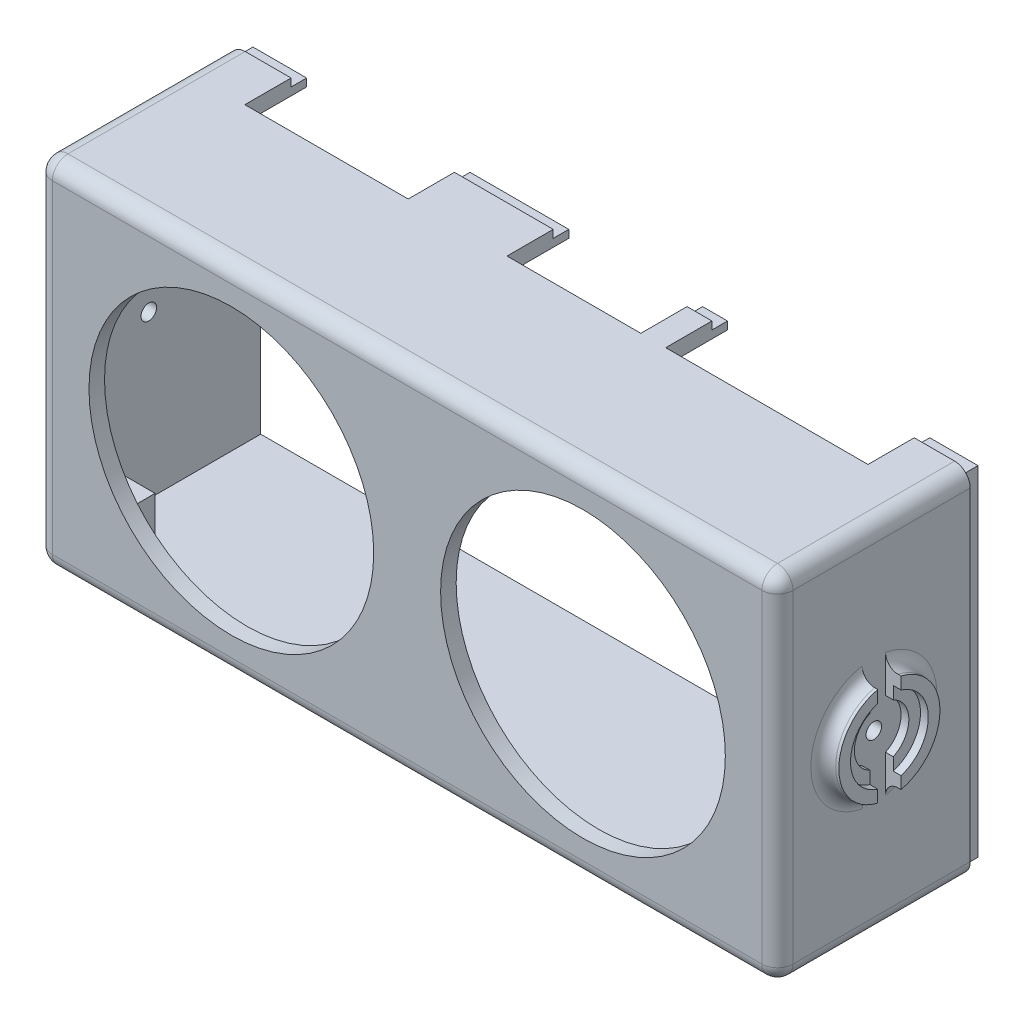
SolidWorks part; units mm, degrees
ref_plane "Спереди" through (0, 0, 0) normal (0, 0, 1) x (1, 0, 0)
ref_plane "Сверху" through (0, 0, 0) normal (0, 1, 0) x (1, 0, 0)
ref_plane "Справа" through (0, 0, 0) normal (1, 0, 0) x (0, 0, -1)
sketch "Эскиз1" plane through (0, 0, 0) normal (0, 0, 1) x (1, 0, 0)
  line L1 (-45.4, -0.2) -> (0.2, -0.2)
  line L2 (-45.4, -0.2) -> (-45.4, 20.6)
  line L3 (-45.4, 20.6) -> (0.2, 20.6)
  line L4 (0.2, -0.2) -> (0.2, 20.6)
  line L5 (1.2, 21.6) -> (-46.4, 21.6)
  line L6 (1.2, 21.6) -> (1.2, -1.2)
  line L7 (1.2, -1.2) -> (-46.4, -1.2)
  line L8 (-46.4, 21.6) -> (-46.4, -1.2)
extrude "Бобышка-Вытянуть1" add sketch "Эскиз1" along normal offset from surface (11.389 mm away) 3 offset beyond the face yes
sketch "Эскиз2" plane through (0, 0, 11.389) normal (0, 0, 1) x (1, 0, 0)
  line L1 (1.2, 21.6) -> (-46.4, 21.6)
  line L2 (1.2, 21.6) -> (1.2, -1.2)
  line L3 (1.2, -1.2) -> (-46.4, -1.2)
  line L4 (-46.4, 21.6) -> (-46.4, -1.2)
extrude "Бобышка-Вытянуть2" add sketch "Эскиз2" along normal blind 1
sketch "Эскиз3" plane through (0, 0, 12.389) normal (0, 0, 1) x (1, 0, 0)
  circle A0 centre (-11.3, 10.2) radius 9.15
  circle A1 centre (-33.9, 10.2) radius 9.15
  dimension "D1" = 18.3
extrude "Вырез-Вытянуть1" cut sketch "Эскиз3" against normal up to surface (1 mm away) up to face at (-22.6, 10.2, 11.389)
sketch "Эскиз7" plane through (0, 21.6, 0) normal (0, 1, 0) x (1, 0, 0)
  line L0 (-42.1499, -2.6711) -> (-32.2499, -2.6711) construction
  line L1 (-25.2999, -2.6711) -> (-17.2999, -2.6711) construction
  line L2 (-15.1001, -2.6711) -> (-2.7001, -2.6711) construction
  line L3 (1.2, 0) -> (-46.4, 0) construction
  line L4 (-2.4001, 0) -> (-15.4001, 0)
  line L5 (-2.4001, 0) -> (-2.4001, -2.9711)
  line L6 (-2.4001, -2.9711) -> (-15.4001, -2.9711)
  line L7 (-15.4001, 0) -> (-15.4001, -2.9711)
  line L9 (-16.9999, 0) -> (-25.5999, 0)
  line L10 (-16.9999, 0) -> (-16.9999, -2.9711)
  line L11 (-16.9999, -2.9711) -> (-25.5999, -2.9711)
  line L12 (-25.5999, 0) -> (-25.5999, -2.9711)
  line L13 (-31.9499, 0) -> (-42.4499, 0)
  line L14 (-31.9499, 0) -> (-31.9499, -2.9711)
  line L15 (-31.9499, -2.9711) -> (-42.4499, -2.9711)
  line L16 (-42.4499, 0) -> (-42.4499, -2.9711)
  dimension "D1" = 0.3
  dimension "D2" = 0.3
  dimension "D3" = 0.3
  dimension "D4" = 0.3
  dimension "D5" = 0.3
  dimension "D6" = 0.3
  dimension "D7" = 0.3
  dimension "D8" = 0.3
  dimension "D9" = 0.3
extrude "Вырез-Вытянуть2" cut sketch "Эскиз7" against normal up to surface (1 mm away) up to face at (-22.6, 20.6, 5.6945)
sketch "Эскиз8" plane through (1.2, 0, 0) normal (1, 0, 0) x (0, 0, -1)
  line L0 (-12.389, 10.2) -> (0, 10.2) construction
  line L1 (-12.389, -1.2) -> (-12.389, 21.6) construction
  line L2 (0, -1.2) -> (0, 21.6) construction
  line L3 (-6.1945, 21.6) -> (-6.1945, -1.2) construction
  line L4 (-12.389, 21.6) -> (0, 21.6) construction
  line L5 (-12.389, -1.2) -> (0, -1.2) construction
  circle A0 centre (-6.1945, 10.2) radius 1.75
  circle A1 centre (-6.1945, 10.2) radius 3.25
  dimension "D1" = 3.5
  dimension "D2" = 1.5
extrude "Бобышка-Вытянуть3" add sketch "Эскиз8" along normal blind 1
sketch "Эскиз9" plane through (2.2, 0, 0) normal (1, 0, 0) x (0, 0, -1)
  line L1 (-6.9445, 6.95) -> (-5.4445, 6.95)
  line L2 (-6.9445, 6.95) -> (-6.9445, 13.45)
  line L3 (-6.9445, 13.45) -> (-5.4445, 13.45)
  line L4 (-5.4445, 6.95) -> (-5.4445, 13.45)
  line L5 (-6.9445, 6.95) -> (-5.4445, 13.45) construction
  line L6 (-6.9445, 13.45) -> (-5.4445, 6.95) construction
  circle A0 centre (-6.1945, 10.2) radius 3.25 construction
  point P0 (-6.1945, 10.2)
  dimension "D1" = 1.5
extrude "Вырез-Вытянуть3" cut sketch "Эскиз9" against normal up to surface (1 mm away) up to face at (1.2, 10.2, 2.9445)
sketch "Эскиз10" plane through (2.2, 0, 0) normal (1, 0, 0) x (0, 0, -1)
  line L0 (-4.4445, 10.2) -> (-2.9445, 10.2) construction
  arc A1 (-5.4445, 8.6189) -> (-5.4445, 11.7811) centre (-6.1945, 10.2) ccw construction
  arc A2 (-5.4445, 7.0377) -> (-5.4445, 13.3623) centre (-6.1945, 10.2) ccw construction
  circle A3 centre (-6.1945, 10.2) radius 2.5
  point P2 (-3.6945, 10.2)
extrude "Вырез-Вытянуть6" cut sketch "Эскиз10" against normal blind 0.5
sketch "Эскиз13" plane through (1.2, 0, 0) normal (1, 0, 0) x (0, 0, -1)
  circle A0 centre (-6.1945, 10.2) radius 0.5
  dimension "D1" = 1
extrude "Вырез-Вытянуть7" cut sketch "Эскиз13" against normal up to surface (1 mm away) up to face at (0.2, 10.2, 5.6945)
sketch "Эскиз15" plane through (-46.4, 0, 0) normal (-1, 0, 0) x (0, 0, 1)
  line L0 (0, 10.2) -> (12.389, 10.2) construction
  line L1 (0, 21.6) -> (0, -1.2) construction
  line L2 (12.389, 21.6) -> (12.389, -1.2) construction
  line L3 (6.1945, 21.6) -> (6.1945, -1.2) construction
  line L4 (12.389, 21.6) -> (0, 21.6) construction
  line L5 (12.389, -1.2) -> (0, -1.2) construction
  circle A0 centre (6.1945, 10.2) radius 1.75
  circle A1 centre (6.1945, 10.2) radius 3.25
  dimension "D1" = 3.5
  dimension "D2" = 1.5
extrude "Бобышка-Вытянуть4" add sketch "Эскиз15" along normal blind 1
sketch "Эскиз16" plane through (-47.4, 0, 0) normal (-1, 0, 0) x (0, 0, 1)
  line L0 (2.9445, 10.2) -> (4.4445, 10.2) construction
  circle A0 centre (6.1945, 10.2) radius 3.25 construction
  circle A1 centre (6.1945, 10.2) radius 1.75 construction
  circle A2 centre (6.1945, 10.2) radius 2.5
  point P9 (3.6945, 10.2)
extrude "Вырез-Вытянуть8" cut sketch "Эскиз16" against normal blind 0.5
sketch "Эскиз17" plane through (-47.4, 0, 0) normal (-1, 0, 0) x (0, 0, 1)
  line L1 (6.9445, 6.95) -> (5.4445, 6.95)
  line L2 (6.9445, 6.95) -> (6.9445, 13.45)
  line L3 (6.9445, 13.45) -> (5.4445, 13.45)
  line L4 (5.4445, 6.95) -> (5.4445, 13.45)
  line L5 (6.9445, 6.95) -> (5.4445, 13.45) construction
  line L6 (6.9445, 13.45) -> (5.4445, 6.95) construction
  circle A0 centre (6.1945, 10.2) radius 3.25 construction
  point P0 (6.1945, 10.2)
  dimension "D1" = 1.5
extrude "Вырез-Вытянуть9" cut sketch "Эскиз17" against normal up to surface (1 mm away) up to face at (-46.4, 10.2, 9.4445)
sketch "Эскиз18" plane through (-46.4, 0, 0) normal (-1, 0, 0) x (0, 0, 1)
  circle A0 centre (6.1945, 10.2) radius 0.5
  dimension "D1" = 1
extrude "Вырез-Вытянуть10" cut sketch "Эскиз18" against normal up to surface (1 mm away) up to face at (-45.4, 10.2, 5.6945)
sketch "Эскиз19" plane through (0, 0, 0) normal (0, 0, -1) x (-1, 0, 0)
  line L0 (-1.2, 21.6) -> (-0.2, 20.6) construction
  line L1 (45.4, -0.2) -> (46.4, -1.2) construction
  line L2 (15.4001, 21.1) -> (15.4001, 20.6)
  line L3 (45.4, -0.2) -> (-0.2, -0.2)
  line L4 (45.4, -0.2) -> (45.4, 20.6)
  line L5 (45.4, 20.6) -> (42.4499, 20.6)
  line L6 (-0.2, -0.2) -> (-0.2, 20.6)
  line L7 (-0.7, 21.1) -> (2.4001, 21.1)
  line L8 (-0.7, 21.1) -> (-0.7, -0.7)
  line L9 (-0.7, -0.7) -> (45.9, -0.7)
  line L10 (45.9, 21.1) -> (45.9, -0.7)
  line L11 (15.4001, 20.6) -> (15.4001, 21.6) construction
  line L12 (16.9999, 21.1) -> (16.9999, 20.6)
  line L13 (16.9999, 20.6) -> (16.9999, 21.6) construction
  line L14 (2.4001, 21.1) -> (2.4001, 20.6)
  line L15 (2.4001, 20.6) -> (2.4001, 21.6) construction
  line L16 (25.5999, 21.1) -> (25.5999, 20.6)
  line L17 (25.5999, 20.6) -> (25.5999, 21.6) construction
  line L18 (31.9499, 21.1) -> (31.9499, 20.6)
  line L21 (31.9499, 20.6) -> (31.9499, 21.6) construction
  line L22 (42.4499, 21.1) -> (42.4499, 20.6)
  line L23 (42.4499, 20.6) -> (42.4499, 21.6) construction
  line L24 (42.4499, 21.1) -> (45.9, 21.1)
  line L25 (31.9499, 20.6) -> (25.5999, 20.6)
  line L26 (25.5999, 21.1) -> (31.9499, 21.1)
  line L27 (16.9999, 20.6) -> (15.4001, 20.6)
  line L28 (15.4001, 21.1) -> (16.9999, 21.1)
  line L29 (2.4001, 20.6) -> (-0.2, 20.6)
extrude "Бобышка-Вытянуть5" add sketch "Эскиз19" along normal blind 1
fillet "Скругление1" radius 0.8 4 edges at (1.2, 10.2, 9.4445) (1.2, 10.2, 2.9445) (-46.4, 10.2, 9.4445) (-46.4, 10.2, 2.9445)
fillet "Скругление2" radius 1 8 edges at (-46.4, -1.2, 6.1945) (-22.6, -1.2, 12.389) (1.2, -1.2, 6.1945) (1.2, 10.2, 12.389) (1.2, 21.6, 6.1945) (-46.4, 21.6, 6.1945) (-46.4, 10.2, 12.389) (-22.6, 21.6, 12.389)
sketch "Эскиз20" plane through (0, 0, 11.389) normal (0, 0, -1) x (-1, 0, 0)
  line L0 (22.6, 20.4) -> (22.6, 0) construction
  line L5 (0, 20.4) -> (45.2, 20.4) construction
  line L6 (45.2, 0) -> (0, 0) construction
  line L7 (-0.2, 10.2) -> (45.4, 10.2) construction
  line L8 (-0.2, 20.6) -> (2.9, 20.6)
  line L9 (-0.2, 20.6) -> (-0.2, 17.4)
  line L10 (-0.2, 17.4) -> (2.9, 17.4)
  line L11 (2.9, 20.6) -> (2.9, 17.4)
  line L12 (-0.2, 20.6) -> (-0.2, -0.2) construction
  line L13 (45.4, -0.2) -> (45.4, 20.6) construction
  line L14 (2.9, -0.2) -> (2.9, 3)
  line L15 (-0.2, 3) -> (2.9, 3)
  line L16 (-0.2, -0.2) -> (-0.2, 3)
  line L17 (-0.2, -0.2) -> (2.9, -0.2)
  line L18 (45.4, -0.2) -> (42.3, -0.2)
  line L19 (45.4, -0.2) -> (45.4, 3)
  line L20 (45.4, 3) -> (42.3, 3)
  line L21 (42.3, -0.2) -> (42.3, 3)
  line L22 (42.3, 20.6) -> (42.3, 17.4)
  line L23 (45.4, 17.4) -> (42.3, 17.4)
  line L24 (45.4, 20.6) -> (45.4, 17.4)
  line L25 (45.4, 20.6) -> (42.3, 20.6)
  circle A0 centre (1.4, 18.9) radius 0.7
  circle A1 centre (1.4, 1.5) radius 0.7
  circle A2 centre (43.8, 1.5) radius 0.7
  circle A3 centre (43.8, 18.9) radius 0.7
  dimension "D1" = 1.4
  dimension "D2" = 1.5
  dimension "D3" = 1.5
extrude "Бобышка-Вытянуть6" add sketch "Эскиз20" along normal blind 2.5
